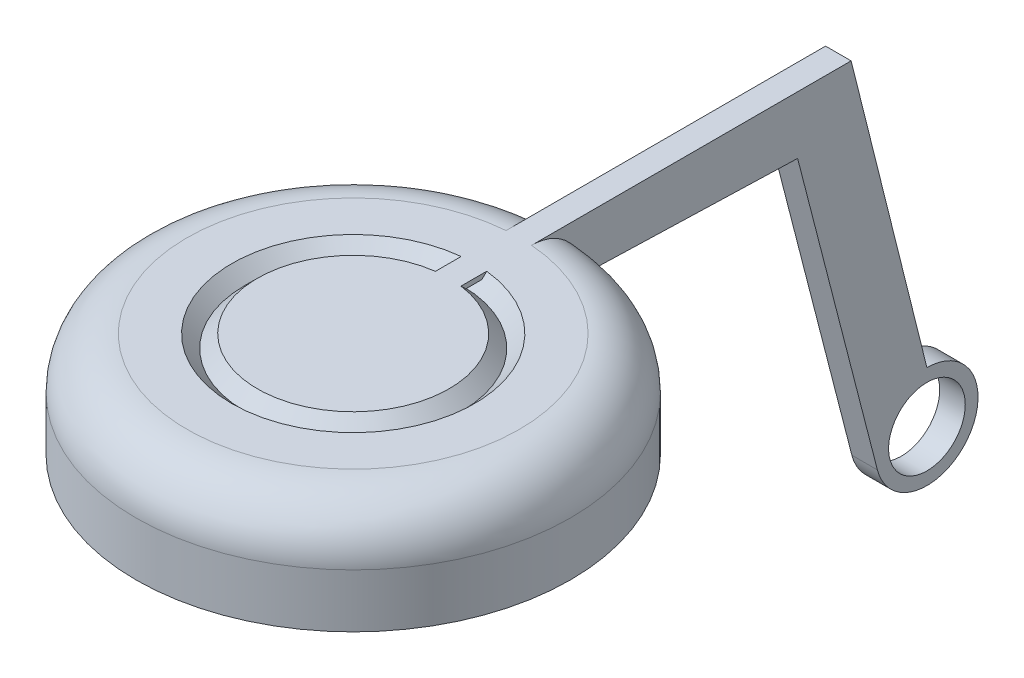
SolidWorks part; units mm, degrees
ref_plane "Front Plane" through (0, 0, 0) normal (0, 0, 1) x (1, 0, 0)
ref_plane "Top Plane" through (0, 0, 0) normal (0, 1, 0) x (1, 0, 0)
ref_plane "Right Plane" through (0, 0, 0) normal (1, 0, 0) x (0, 0, -1)
sketch "Sketch4" plane through (0, 0, 0) normal (1, 0, 0) x (0, 0, -1)
  line L0 (0, 0) -> (-3.75, 0)
  line L1 (-3.75, 0) -> (-4.25, -0.5)
  line L2 (-4.25, -0.5) -> (-4.75, 0)
  line L3 (-4.75, 0) -> (-8.5, 0)
  line L4 (-8.5, 0) -> (-8.5, -4)
  line L5 (-8.5, -4) -> (0, -4)
  line L6 (0, 0) -> (0, -4)
  line L7 (-8.5, -0.5) -> (0, -0.5) construction
  line L8 (0, 1.8905) -> (0, -6.6755) construction
  point P3 (-4.25, -0.5)
  dimension "D1" = 8.5
  dimension "D2" = 0.5
  dimension "D3" = 4
revolve "Revolve1" add sketch "Sketch4" angle 360 about L8
fillet "Fillet1" radius 2 1 edges at (0, 0, 8.5)
sketch "Sketch5" plane through (0, -4, 0) normal (0, -1, 0) x (1, 0, 0)
  circle A0 centre (0, 0) radius 8.5
  circle A1 centre (0, 0) radius 7
  dimension "D1" = 14
extrude "Boss-Extrude1" add sketch "Sketch5" along normal blind 0.1 separate body
sketch "Sketch6" plane through (0, 0, 0) normal (1, 0, 0) x (0, 0, -1)
  line L0 (0, 0) -> (18.9824, 0)
  line L1 (8.5, -2) -> (16.8888, -2.2594)
  line L4 (16.8888, -2.2594) -> (20.0117, -14.3782)
  line L5 (0, 0) -> (0, -0.1877)
  line L6 (0, -0.1877) -> (7.0067, -0.1877)
  line L7 (7.0067, -0.1877) -> (8.5, -2)
  line L8 (3.75, 0) -> (-3.75, 0) construction
  line L9 (18.9824, 0) -> (21.9484, -11.8791)
  circle A0 centre (21.9484, -13.8791) radius 1.5
  circle A1 centre (21.9484, -13.8791) radius 2
  point P4 (21, -6.9701)
  point P5 (21, -6.8235)
  point P6 (21.1544, 0)
  point P7 (19.5965, -4)
  point P13 (8.6677, -2.72)
  point P14 (23, -9.3987)
  point P15 (0, 0)
  point P16 (19.5965, -2)
  point P17 (23, -9.2521)
  point P21 (25, -10.0896)
  point P22 (25, -0.1877)
  point P26 (22.3602, -2)
  point P27 (18.6418, -4.1101)
  point P28 (14.6418, -0.1877)
  point P29 (13.8683, -2)
  point P30 (17.4191, -0.1877)
  point P31 (16.4979, -2)
  point P32 (21, -13.0968)
  point P33 (21, -13.1061)
  point P34 (18.3971, -13.7761)
  point P35 (13.9261, -2.5263)
  point P36 (21.9484, -13.8791)
  point P37 (16.8888, -2.2594)
  point P38 (18.9824, -0.1877)
  dimension "D1" = 3
  dimension "D2" = 4
extrude "Boss-Extrude2" add sketch "Sketch6" along normal blind 0.5 and the other way blind 0.5 contours L0 L5 L6 L7 L1 L4 A1 | A1 A0 region at (0, -0.2624, -9.4912) region at (0, -12.5049, -23.3226)
